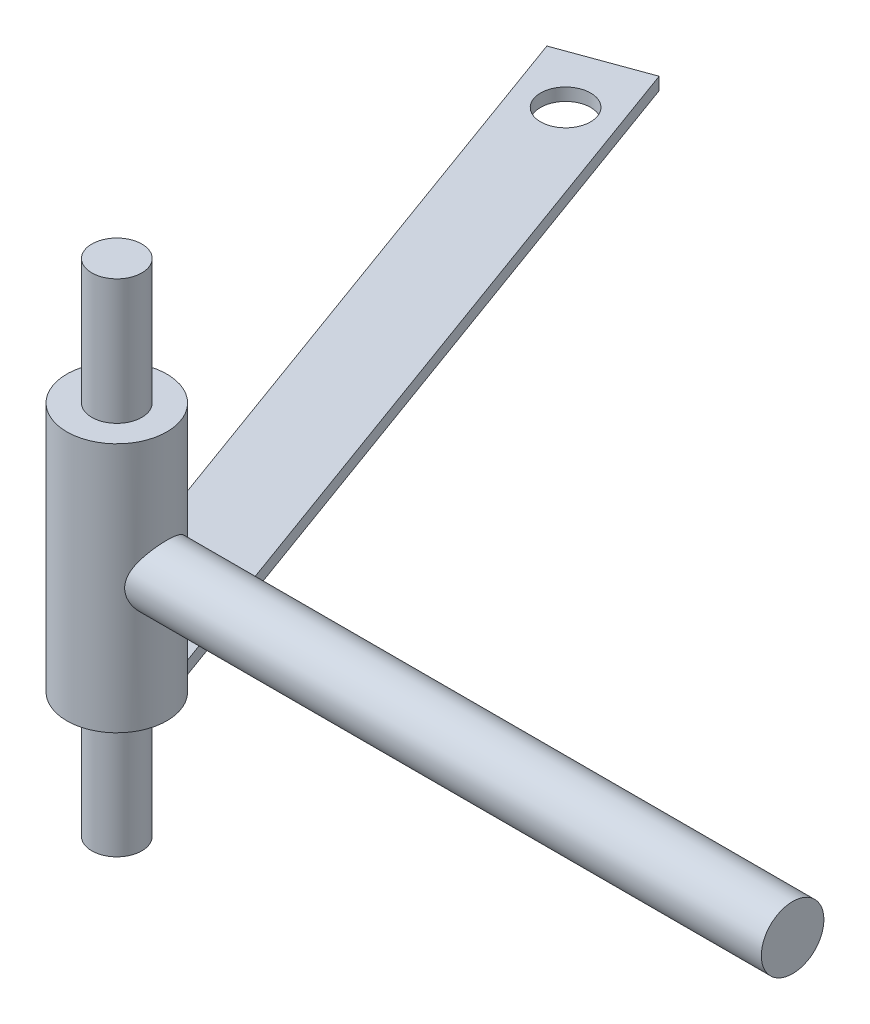
SolidWorks part; units mm, degrees
ref_plane "Front Plane" through (0, 0, 0) normal (0, 0, 1) x (1, 0, 0)
ref_plane "Top Plane" through (0, 0, 0) normal (0, 1, 0) x (1, 0, 0)
ref_plane "Right Plane" through (0, 0, 0) normal (1, 0, 0) x (0, 0, -1)
sketch "Sketch1" plane through (0, 0, 0) normal (0, 1, 0) x (1, 0, 0)
  circle A0 centre (0, 0) radius 4
  dimension "D1" = 8
extrude "Boss-Extrude1" add sketch "Sketch1" along normal mid plane 80
ref_axis "Axis2" through (0, 40, 0) along (0, -1, 0)
ref_plane "Plane1" through (0, 0, 0) normal (0.342, 0, 0.9397) x (0, -1, 0)
sketch "Sketch3" plane through (0, 0, 0) normal (0, 1, 0) x (1, 0, 0)
  circle A0 centre (0, 0) radius 8
  dimension "D1" = 16
extrude "Boss-Extrude2" add sketch "Sketch3" along normal mid plane 40
sketch "Sketch4" plane through (0, 0, 0) normal (1, 0, 0) x (0, 0, -1)
  circle A0 centre (0, 0) radius 5
  dimension "D1" = 10
extrude "Boss-Extrude3" add sketch "Sketch4" along normal blind 108
sketch "Sketch5" plane through (0, 0, 0) normal (0.342, 0, 0.9397) x (0.9397, 0, -0.342)
  line L0 (-8, -20) -> (8, -20) construction
  line L5 (-7, -16) -> (7, -16)
  line L6 (-7, -16) -> (-7, -18)
  line L7 (-7, -18) -> (7, -18)
  line L8 (7, -16) -> (7, -18)
  line L9 (-7, -16) -> (7, -18) construction
  line L10 (-7, -18) -> (7, -16) construction
  point P0 (0, -17)
  dimension "D1" = 14
  dimension "D2" = 2
  dimension "D3" = 2
extrude "Boss-Extrude4" add sketch "Sketch5" against normal blind 130
sketch "Sketch6" plane through (0, -16, 0) normal (0, 1, 0) x (1, 0, 0)
  line L1 (-37.8848, 124.5542) -> (-51.0405, 119.7659) construction
  line L2 (-51.0405, 119.7659) -> (-7.9025, 1.2453) construction
  circle A0 centre (-41.0424, 112.7631) radius 4
  dimension "D1" = 8
  dimension "D2" = 10
  dimension "D3" = 7
extrude "Cut-Extrude1" cut sketch "Sketch6" against normal up to next
ref_axis "Axis1" through (108, 0, 0) along (-1, 0, 0)
